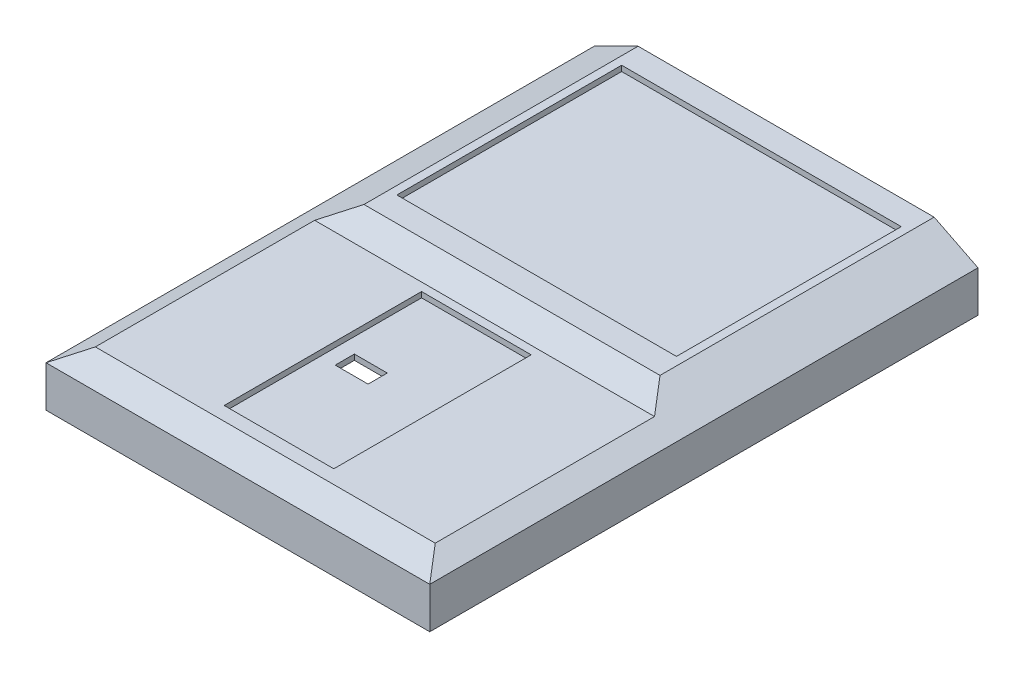
SolidWorks part; units mm, degrees
ref_plane "Ebene vorne" through (0, 0, 0) normal (0, 0, 1) x (1, 0, 0)
ref_plane "Ebene oben" through (0, 0, 0) normal (0, 1, 0) x (1, 0, 0)
ref_plane "Ebene rechts" through (0, 0, 0) normal (1, 0, 0) x (0, 0, -1)
sketch "Skizze1" plane through (0, 0, 0) normal (0, 0, 1) x (1, 0, 0)
  line L1 (-35, -7.5) -> (35, -7.5)
  line L2 (-35, -7.5) -> (-35, 7.5)
  line L3 (-35, 7.5) -> (35, 7.5)
  line L4 (35, -7.5) -> (35, 7.5)
  line L5 (-35, -7.5) -> (35, 7.5) construction
  line L6 (-35, 7.5) -> (35, -7.5) construction
  point P0 (0, 0)
  dimension "D1" = 70
  dimension "D2" = 15
extrude "Aufsatz-Linear austragen1" add sketch "Skizze1" along normal blind 100
sketch "Skizze2" plane through (0, 0, 100) normal (0, 0, 1) x (1, 0, 0)
  line L0 (-35, 7.5) -> (-35, 0)
  line L1 (-35, 7.5) -> (-35, -7.5) construction
  line L2 (-35, 0) -> (-20, 7.5)
  line L3 (35, 7.5) -> (-35, 7.5) construction
  line L4 (-20, 7.5) -> (-35, 7.5)
  dimension "D1" = 15
extrude "Schnitt-Linear austragen1" cut sketch "Skizze2" against normal up to surface (100 mm away) up to face at (0, 0, 0)
ref_plane "Ebene1" through (0, 0, 0) normal (-1, 0, 0) x (0, 0, 1)
mirror "Spiegeln1" about plane through (0, 0, 0) normal (-1, 0, 0) of "Schnitt-Linear austragen1"
sketch "Skizze4" plane through (-35, 0, 0) normal (-1, 0, 0) x (0, 0, 1)
  line L0 (100, 0) -> (95, 2)
  line L1 (95, 2) -> (55, 2)
  line L2 (55, 2) -> (50, 4)
  line L3 (50, 4) -> (0, 4)
  line L5 (0, 7.5) -> (100, 7.5) construction
  line L6 (0, 7.5) -> (100, 7.5)
  line L7 (100, 7.5) -> (100, 0)
  line L8 (0, 0) -> (0, 7.5) construction
  line L9 (0, 4) -> (0, 7.5)
  dimension "D1" = 2
  dimension "D2" = 2
  dimension "D3" = 40
  dimension "D4" = 50
extrude "Schnitt-Linear austragen3" cut sketch "Skizze4" against normal up to surface (70 mm away) up to face at (35, -3.75, 50)
shell "Wandung1" thickness 2 removed face at (0, -7.5, 50)
sketch "Skizze5" plane through (0, 2, 0) normal (0, 1, 0) x (1, 0, 0)
  line L0 (0, 4.125) -> (0, -4.125) construction
  line L1 (-10, -92.5) -> (10, -92.5)
  line L2 (-10, -92.5) -> (-10, -56.5)
  line L3 (-10, -56.5) -> (10, -56.5)
  line L4 (10, -92.5) -> (10, -56.5)
  line L5 (-10, -92.5) -> (10, -56.5) construction
  line L6 (-10, -56.5) -> (10, -92.5) construction
  line L7 (31, -55) -> (-31, -55) construction
  point P0 (0, -74.5)
  dimension "D1" = 36
  dimension "D2" = 20
  dimension "D3" = 1.5
extrude "Schnitt-Linear austragen4" cut sketch "Skizze5" against normal blind 1
sketch "Skizze6" plane through (0, 1, 0) normal (0, 1, 0) x (1, 0, 0)
  line L0 (-10, -56.5) -> (-10, -92.5) construction
  line L1 (-7.25, -71.5) -> (-1.25, -71.5)
  line L2 (-7.25, -71.5) -> (-7.25, -75)
  line L3 (-7.25, -75) -> (-1.25, -75)
  line L4 (-1.25, -71.5) -> (-1.25, -75)
  line L5 (10, -56.5) -> (-10, -56.5) construction
  dimension "D1" = 2.75
  dimension "D2" = 15
  dimension "D3" = 3.5
  dimension "D4" = 6
extrude "Schnitt-Linear austragen5" cut sketch "Skizze6" against normal up to surface (1 mm away) up to face at (0, 0, 74.6148)
sketch "Skizze7" plane through (0, 4, 0) normal (0, 1, 0) x (1, 0, 0)
  line L1 (25.5, -4.5) -> (-25.5, -4.5)
  line L2 (25.5, -4.5) -> (25.5, -45.5)
  line L3 (25.5, -45.5) -> (-25.5, -45.5)
  line L4 (-25.5, -4.5) -> (-25.5, -45.5)
  line L5 (25.5, -4.5) -> (-25.5, -45.5) construction
  line L6 (25.5, -45.5) -> (-25.5, -4.5) construction
  line L7 (27, -50) -> (27, 0) construction
  line L8 (27, 0) -> (-27, 0) construction
  point P0 (0, -25)
  dimension "D1" = 51
  dimension "D2" = 41
  dimension "D3" = 1.5
  dimension "D4" = 4.5
extrude "Schnitt-Linear austragen6" cut sketch "Skizze7" against normal blind 1
sketch "Skizze10" plane through (0, 0, 0) normal (0, 0, -1) x (-1, 0, 0)
  line L0 (7.5, -7.5) -> (-7.5, -7.5)
  line L1 (35, -7.5) -> (-35, -7.5) construction
  line L2 (-7.5, -7.5) -> (-7.5, -5.8)
  line L3 (-7.5, -5.8) -> (-2.5, -5.8)
  line L4 (-2.5, -5.8) -> (-2.5, -4.5)
  line L5 (-2.5, -4.5) -> (2.5, -4.5)
  line L6 (2.5, -4.5) -> (2.5, -5.8)
  line L7 (2.5, -5.8) -> (7.5, -5.8)
  line L8 (7.5, -5.8) -> (7.5, -7.5)
  line L9 (0, -4.125) -> (0, 4.125) construction
  dimension "D1" = 5
  dimension "D2" = 1.3
  dimension "D3" = 2.5
  dimension "D4" = 2.5
  dimension "D5" = 1.7
  dimension "D6" = 1.3
extrude "Schnitt-Linear austragen7" cut sketch "Skizze10" against normal blind 1
